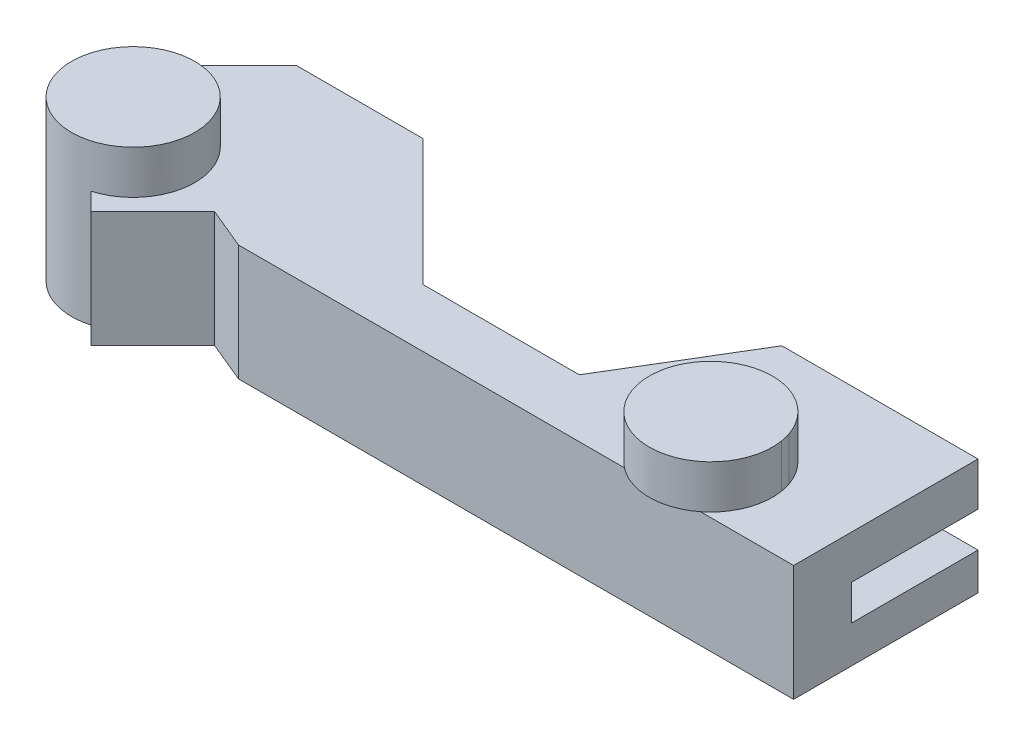
SolidWorks part; units mm, degrees
ref_plane "Front Plane" through (0, 0, 0) normal (0, 0, 1) x (1, 0, 0)
ref_plane "Top Plane" through (0, 0, 0) normal (0, 1, 0) x (1, 0, 0)
ref_plane "Right Plane" through (0, 0, 0) normal (1, 0, 0) x (0, 0, -1)
sketch "Sketch2" plane through (0, 0, 0) normal (0, 1, 0) x (1, 0, 0)
  line L0 (0, 0) -> (24.28, 0)
  line L1 (0, 0) -> (-8.7186, 8.7186)
  line L2 (34.1907, 0) -> (38.28, 0)
  line L4 (38.28, -4) -> (31.8721, -4)
  line L6 (-2.8284, -2.8284) -> (0, -4)
  line L7 (33.4327, 0) -> (25.038, 0)
  line L8 (-8.7186, 8.7186) -> (-11.5615, 5.8758)
  line L9 (38.28, 0) -> (38.28, -4)
  line L10 (-8.7186, 8.7186) -> (0, 8.7186)
  line L11 (0, 8.7186) -> (8.7186, 0)
  line L12 (38.28, 0) -> (38.28, 8.7186)
  line L13 (38.28, 8.7186) -> (24.7552, 8.7186)
  line L17 (19.4998, 0) -> (24.7552, 8.7186)
  line L18 (25.038, 0) -> (24.28, 0)
  line L19 (33.4327, 0) -> (34.1907, 0)
  line L20 (26.5985, -4) -> (0, -4)
  line L21 (-2.8284, -2.8284) -> (-7.0815, -7.0815)
  line L22 (-7.0815, -7.0815) -> (-8.2939, -5.8691)
  line L23 (31.8721, -4) -> (26.5985, -4)
  line L24 (-15.7482, 1.5852) -> (-11.5615, 5.8758)
  line L25 (-13.5631, -0.5999) -> (-15.7482, 1.5852)
  arc A2 (33.4327, 0) -> (25.038, 0) centre (29.2353, -0.6669) ccw
  circle A3 centre (-9.4828, -1.7888) radius 4.25
  arc A4 (26.5985, -4) -> (31.8721, -4) centre (29.2353, -0.6669) ccw
  dimension "D5" = 8.5
  dimension "D6" = 8.5
  dimension "D1" = 14
  dimension "D2" = 12.33
  dimension "D3" = 4
  dimension "D4" = 4
extrude "Boss-Extrude1" add sketch "Sketch2" along normal blind 6 contours A3 | A2 region at (29.2353, 0, -1.5023) region at (-9.4828, 0, 1.7888)
extrude "Boss-Extrude2" add sketch "Sketch2<7>" along normal blind 3 contours A3 L22 L21 L6 L20 A2 L18 L0 L1 L8 L24 L25 | L11 L10 L1 L0 | A2 L19 L2 L12 L13 L17 L0 L18 | A2 L4 L9 L2 L19 region at (0, 0, -4.3593) region at (9.9412, 0, 0.6857) region at (30.3052, 0, -4.6272)
sketch "Sketch2<7>" plane through (0, 0, 0) normal (0, 1, 0) x (1, 0, 0) same geometry as "Sketch2"
extrude "Boss-Extrude3" add sketch "Sketch2<9>" against normal blind 5 contours A3 L22 L21 L6 L20 L23 L4 L9 L2 L19 L7 L18 L0 L1 L8 L24 L25 | A3 region at (9.9412, 0, 0.6857) region at (-9.4828, 0, 1.7888)
sketch "Sketch2<9>" plane through (0, 0, 0) normal (0, 1, 0) x (1, 0, 0) same geometry as "Sketch2"
ref_plane "Plane1" through (0, -5, 0) normal (0, -1, 0) x (-1, 0, 0)
sketch "Sketch3" plane through (0, -5, 0) normal (0, -1, 0) x (-1, 0, 0)
  line L0 (-38.28, -4) -> (-38.28, 8.7186)
  line L1 (-38.28, 8.7186) -> (-24.7552, 8.7186)
  line L2 (-24.7552, 8.7186) -> (-19.4998, 0)
  line L3 (0, 0) -> (-38.28, 0) construction
  line L4 (-19.4998, 0) -> (-24.7552, 8.7186) construction
  line L5 (-19.4998, 0) -> (-8.7186, 0)
  line L6 (0, 0) -> (-8.7186, 0) construction
  line L7 (-8.7186, 0) -> (0, 8.7186)
  line L8 (0, 8.7186) -> (8.7186, 8.7186)
  line L9 (8.7186, 8.7186) -> (15.7482, 1.5852)
  line L10 (15.7482, 1.5852) -> (13.5631, -0.5999)
  line L11 (13.5631, -0.5999) -> (7.0815, -7.0815)
  line L12 (7.0815, -7.0815) -> (2.8284, -2.8284)
  line L13 (2.8284, -2.8284) -> (0, -4)
  line L14 (0, -4) -> (-38.28, -4)
extrude "Boss-Extrude4" add sketch "Sketch3" against normal blind 2.56
ref_plane "Plane2" through (0, 3, 0) normal (0, 1, 0) x (1, 0, 0)
sketch "Sketch4" plane through (0, 3, 0) normal (0, 1, 0) x (1, 0, 0)
  line L0 (29.2353, 0) -> (29.2353, -0.66)
  line L1 (25.038, 0) -> (33.4327, 0) construction
  circle A0 centre (29.2353, -0.66) radius 4.2478
  dimension "D1" = 0.66
extrude "Boss-Extrude5" add sketch "Sketch4" along normal blind 3 contours A0 region at (25.1077, 3, 0.66)
